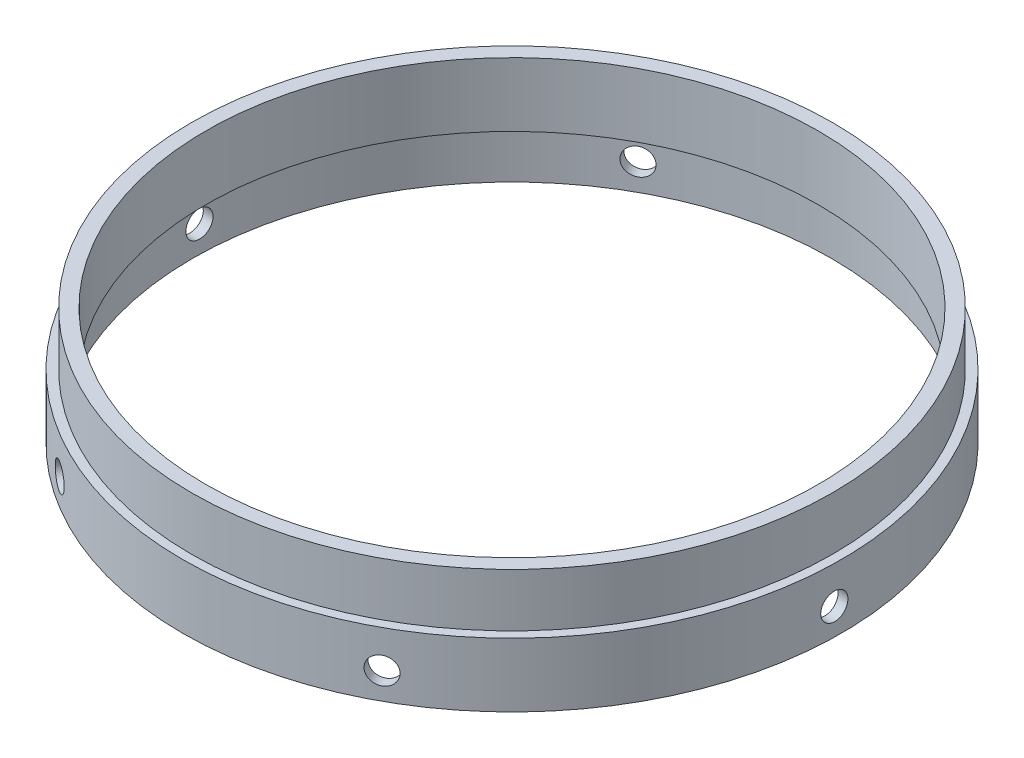
SolidWorks part; units mm, degrees
material "6061-T6 (SS)"
ref_plane "Front Plane" through (0, 0, 0) normal (0, 0, 1) x (1, 0, 0)
ref_plane "Top Plane" through (0, 0, 0) normal (0, 1, 0) x (1, 0, 0)
ref_plane "Right Plane" through (0, 0, 0) normal (1, 0, 0) x (0, 0, -1)
ref_axis "Axis1" through (0, -55, 0) along (0, 1, 0)
sketch "Sketch1" plane through (0, 0, 0) normal (0, 0, 1) x (1, 0, 0)
  line L0 (78.5876, 0) -> (78.5876, 15.24)
  line L1 (78.5876, 15.24) -> (76.454, 15.24)
  line L2 (76.454, 15.24) -> (76.454, 27.94)
  line L3 (76.454, 27.94) -> (73.025, 27.94)
  line L4 (73.025, 27.94) -> (73.025, 12.7)
  line L5 (73.025, 12.7) -> (76.2, 12.7)
  line L6 (76.2, 12.7) -> (76.2, 0)
  line L7 (76.2, 0) -> (78.5876, 0)
  line L8 (0, -55) -> (0, 55) construction
  line L9 (55, 0) -> (-55, 0) construction
  dimension "D1" = 78.5876
  dimension "D2" = 76.2
  dimension "D3" = 76.454
  dimension "D4" = 2.54
  dimension "D5" = 73.025
  dimension "D6" = 12.7
  dimension "D7" = 12.7
revolve "Revolve1" add sketch "Sketch1" angle 360 about axis through (0, -55, 0) along (0, 1, 0)
hole_wizard "1/4 (0.25) Diameter Hole1" positions "3DSketch1" profile "Sketch2" hole size "1/4" standard "ANSI Inch" end condition up to next
sketch3d "3DSketch1"
  point P0 (37.8571, 6.35, 68.8684)
  dimension "D1" = 6.35
sketch "Sketch2" plane through (37.8571, 6.35, 68.8684) normal (0, 1, 0) x (0.8763, 0, -0.4817)
  line L0 (0, 0) -> (0, 183.2424)
  line L1 (0, 183.2424) -> (3.175, 183.2424)
  line L2 (3.175, 183.2424) -> (3.175, 0)
  line L5 (3.175, 0) -> (0, 0)
  line L11 (0, -6.35) -> (0, 107.95) construction
  dimension "Thru Hole Dia." = 6.35
  dimension "Thru Hole Depth" = 183.2424
pattern_circular "CirPattern1" count 6 over 360 about axis through (0, -55, 0) along (0, 1, 0) of "1/4 (0.25) Diameter Hole1"
